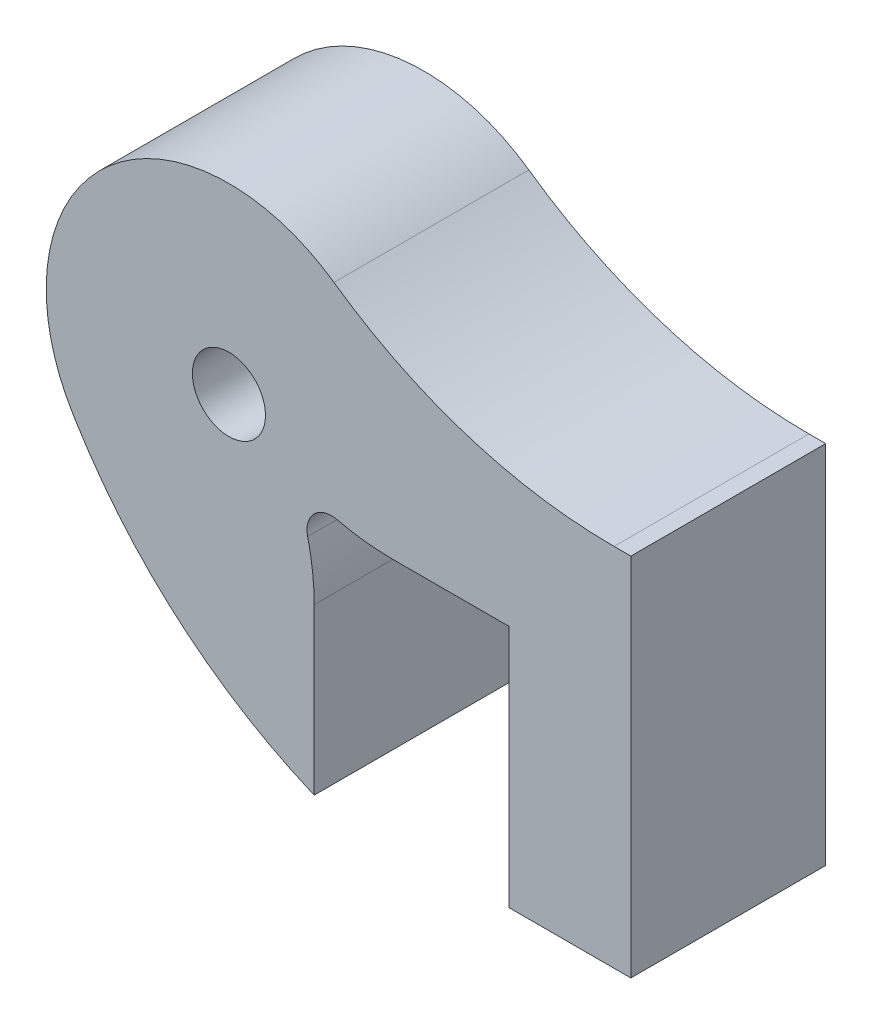
SolidWorks part; units mm, degrees
material "PMMA"
ref_plane "Front Plane" through (0, 0, 0) normal (0, 0, 1) x (1, 0, 0)
ref_plane "Top Plane" through (0, 0, 0) normal (0, 1, 0) x (1, 0, 0)
ref_plane "Right Plane" through (0, 0, 0) normal (1, 0, 0) x (0, 0, -1)
sketch "Sketch1" plane through (0, 0, 0) normal (0, 0, 1) x (1, 0, 0)
  line L0 (7, 10) -> (0, 15) construction
  line L1 (20, 0) -> (15, 0)
  line L2 (20, 0) -> (20, 15)
  line L3 (20, 15) -> (0, 15)
  line L4 (0, 0) -> (0, 15)
  line L7 (7, 0) -> (0, 0)
  line L9 (15, 0) -> (15, 10)
  line L10 (15, 10) -> (7, 10)
  line L11 (7, 0) -> (7, 10)
  circle A0 centre (3.5, 12.5) radius 1.5
  dimension "D3" = 3
  dimension "D1" = 20
  dimension "D2" = 5
  dimension "D4" = 10
  dimension "D5" = 8
  dimension "D6" = 5
extrude "Boss-Extrude1" add sketch "Sketch1" along normal blind 8
sketch "Sketch2" plane through (0, 0, 8) normal (0, 0, 1) x (1, 0, 0)
  line L0 (7, 10) -> (7.7071, 9.2929) construction
  line L1 (7, 0) -> (7, 10) construction
  line L3 (0, 0) -> (7, 0)
  line L4 (0, 0) -> (0, 1)
  line L5 (0, 1) -> (7, 1)
  line L6 (7, 0) -> (7, 1)
  circle A0 centre (7.7071, 9.2929) radius 1
  line M6 (7, 0) -> (7, 10)
  line M7 (7, 10) -> (15, 10)
  dimension "D1" = 2
  dimension "D2" = 45
  dimension "D3" = 1
extrude "Cut-Extrude1" cut sketch "Sketch2" against normal through all contours A0 M6 M7 | A0 region at (7.7988, 9.2012, 8)
fillet "Fillet1" radius 10 2 edges at (7, 8.5858, 4) (8.4142, 10, 4)
sketch "Sketch3" plane through (0, 0, 8) normal (0, 0, 1) x (1, 0, 0)
  circle A0 centre (3.5, 12.5) radius 7.5
  circle A1 centre (3.5, 12.5) radius 1.5 construction
  line M9 (20, 15) -> (0, 15)
  line M10 (0, 15) -> (0, 0)
  dimension "D1" = 15
extrude "Boss-Extrude2" add sketch "Sketch3" against normal blind 8 contours A0 M9 M10 region at (5.2855, 15.203, 8)
fillet "Fillet2" radius 20 2 edges at (10.5711, 15, 4) (0, 5.8668, 4)
fillet "Fillet3" radius 21 1 edges at (0, 0, 4)
